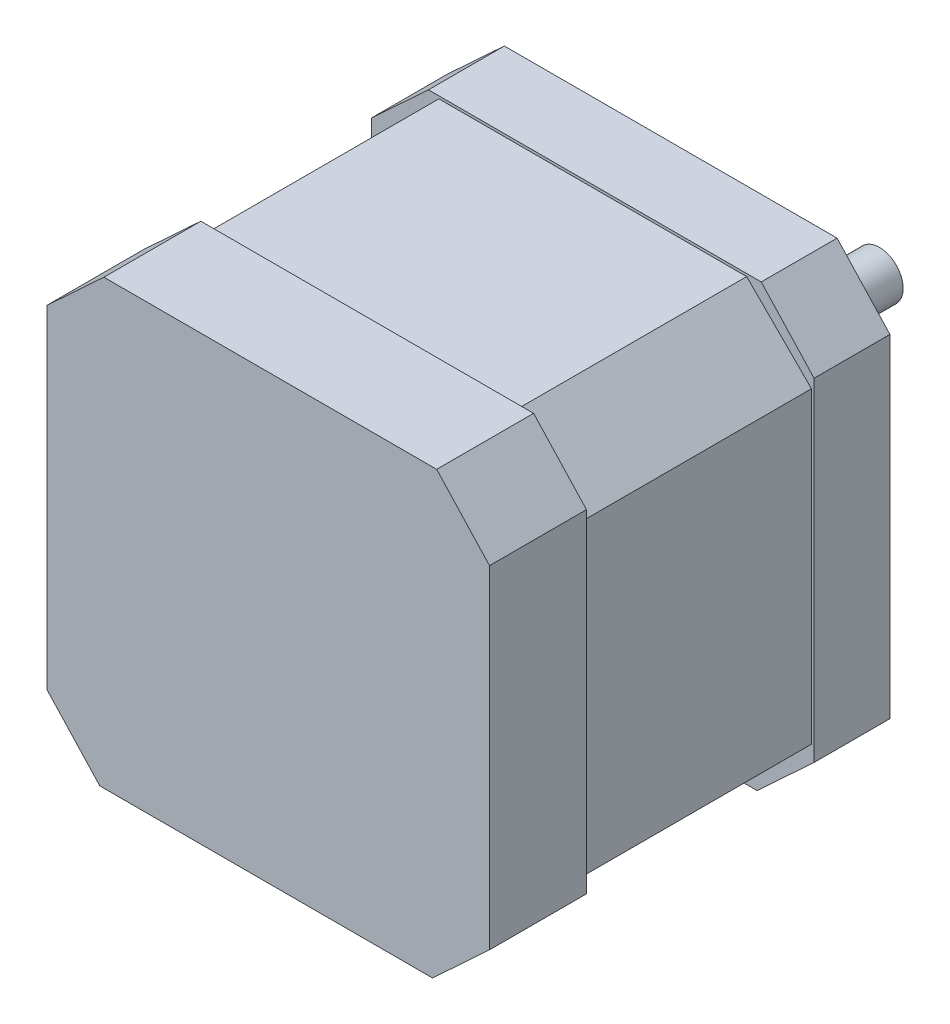
SolidWorks part; units mm, degrees
material "Ferro dúctil"
ref_plane "Plano frontal" through (0, 0, 0) normal (0, 0, 1) x (1, 0, 0)
ref_plane "Plano superior" through (0, 0, 0) normal (0, 1, 0) x (1, 0, 0)
ref_plane "Plano direito" through (0, 0, 0) normal (1, 0, 0) x (0, 0, -1)
sketch "Esboço1" plane through (0, 0, 0) normal (0, 0, 1) x (1, 0, 0)
  line L0 (-1.3818, -36.7436) -> (-36.7436, 1.3818)
  line L1 (-21, 21) -> (21, 21)
  line L2 (-21, 21) -> (-21, -21)
  line L3 (-21, -21) -> (21, -21)
  line L4 (21, 21) -> (21, -21)
  line L5 (-21, 21) -> (21, -21) construction
  line L6 (-21, -21) -> (21, 21) construction
  line L7 (-1.3818, -36.7436) -> (36.7436, -1.3818)
  line L8 (-36.7436, 1.3818) -> (1.3818, 36.7436)
  line L9 (36.7436, -1.3818) -> (1.3818, 36.7436)
  line L10 (-1.3818, -36.7436) -> (1.3818, 36.7436) construction
  line L11 (-36.7436, 1.3818) -> (36.7436, -1.3818) construction
  point P0 (0, 0)
  point P7 (0, 0)
  dimension "D1" = 42
  dimension "D2" = 52
extrude "Ressalto-extrusão1" add sketch "Esboço1" along normal blind 38 contours L4 L9 L1 L8 L2 L0 L3 L7 region at (0, 0, 0)
sketch "Esboço2" plane through (0, 0, 38) normal (0, 0, 1) x (1, 0, 0)
  line L1 (-20.75, -20.75) -> (20.75, -20.75)
  line L2 (-20.75, -20.75) -> (-20.75, 20.75)
  line L3 (-20.75, 20.75) -> (20.75, 20.75)
  line L4 (20.75, -20.75) -> (20.75, 20.75)
  line L5 (-20.75, -20.75) -> (20.75, 20.75) construction
  line L6 (-20.75, 20.75) -> (20.75, -20.75) construction
  line L7 (0, -35.3553) -> (-35.3553, 0)
  line L8 (0, -35.3553) -> (35.3553, 0)
  line L9 (-35.3553, 0) -> (0, 35.3553)
  line L10 (35.3553, 0) -> (0, 35.3553)
  line L11 (0, -35.3553) -> (0, 35.3553) construction
  line L12 (-35.3553, 0) -> (35.3553, 0) construction
  point P0 (0, 0)
  point P8 (-17.6777, 17.6777)
  point P9 (0, 0)
  dimension "D1" = 50
  dimension "D2" = 41.5
extrude "Corte-Extrusão-Fina1" cut sketch "Esboço2" against normal offset from surface (21.6 mm away) 7.2 from offset 9.2 thin contours L4 L10 L3 L9 L2 L7 L1 L8 up to face at (0, 0, 0) offset against normal yes thin type one direction wall 10
sketch "Esboço3" plane through (0, 0, 0) normal (0, 0, -1) x (-1, 0, 0)
  circle A0 centre (0, 0) radius 2.25
  dimension "D1" = 4.5
extrude "Ressalto-extrusão2" add sketch "Esboço3" along normal blind 20
sketch "Esboço4" plane through (0, 0, 0) normal (0, 0, -1) x (-1, 0, 0)
  circle A0 centre (0, 0) radius 10
  dimension "D1" = 20
extrude "Ressalto-extrusão3" add sketch "Esboço4" along normal blind 2
sketch "Esboço5" plane through (0, 0, 0) normal (0, 0, -1) x (-1, 0, 0)
  line L1 (15.5, 15.5) -> (-15.5, 15.5) construction
  line L2 (15.5, 15.5) -> (15.5, -15.5) construction
  line L3 (15.5, -15.5) -> (-15.5, -15.5) construction
  line L4 (-15.5, 15.5) -> (-15.5, -15.5) construction
  line L5 (15.5, 15.5) -> (-15.5, -15.5) construction
  line L6 (15.5, -15.5) -> (-15.5, 15.5) construction
  circle A0 centre (15.5, -15.5) radius 1.5
  circle A1 centre (-15.5, -15.5) radius 1.5
  circle A2 centre (-15.5, 15.5) radius 1.5
  circle A3 centre (15.5, 15.5) radius 1.5
  point P0 (0, 0)
  dimension "D1" = 3
  dimension "D2" = 31
extrude "Corte-extrusão1" cut sketch "Esboço5" against normal blind 10
